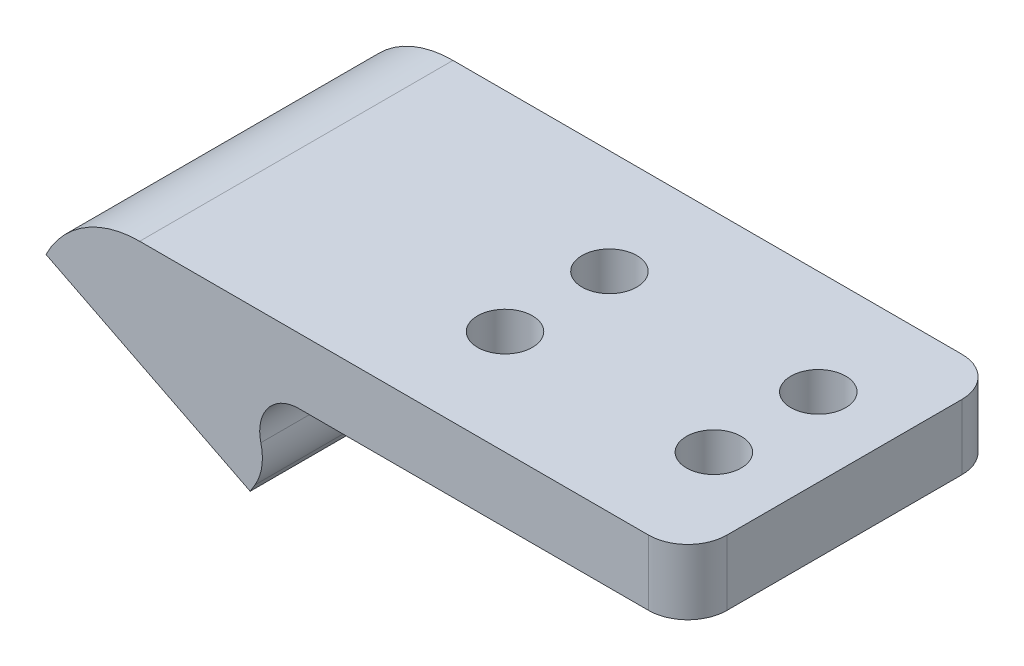
SolidWorks part; units mm, degrees
ref_plane "Plan de face" through (0, 0, 0) normal (0, 0, 1) x (1, 0, 0)
ref_plane "Plan de dessus" through (0, 0, 0) normal (0, 1, 0) x (1, 0, 0)
ref_plane "Plan de droite" through (0, 0, 0) normal (1, 0, 0) x (0, 0, -1)
sketch "Esquisse1" plane through (0, 0, 0) normal (0, 0, 1) x (1, 0, 0)
  line L1 (-6.5596, 0) -> (10.4404, 0)
  line L2 (-6.5596, 0) -> (-6.5596, 5)
  line L3 (-6.5596, 5) -> (10.4404, 5)
  line L4 (10.4404, 0) -> (10.4404, 5)
  dimension "D1" = 5
  dimension "D2" = 17
extrude "Boss.-Extru.1" add sketch "Esquisse1" along normal blind 24
sketch "Esquisse2" plane through (0, 0, 24) normal (0, 0, 1) x (1, 0, 0)
  line L0 (-6.5596, 5) -> (-16.4711, 5)
  line L1 (-16.4711, 5) -> (-0.5016, -3.0561)
  line L2 (-16.4711, 5) -> (-18.7231, 0.5359)
  line L3 (-18.7231, 0.5359) -> (-3.0805, -7.3553)
  line L4 (-3.0805, -7.3553) -> (-0.5016, -3.0561)
  line L5 (-6.5596, 5) -> (-6.5596, 0) construction
  line M4 (-6.5596, 5) -> (-6.5596, 0)
extrude "Boss.-Extru.2" add sketch "Esquisse2" against normal blind 24 contours L3 L4 L1 L2 | L0 L1 M4 region at (-9.8634, 3.3333, 24) region at (-9.6899, -1.2113, 24)
fillet "Congé1" radius 4 1 edges at (-0.5016, -3.0561, 12)
fillet "Congé2" radius 8 1 edges at (-16.4711, 5, 12)
fillet "Congé3" radius 3 1 edges at (-6.5596, 0, 12)
sketch "Esquisse3" plane through (10.4404, 0, 0) normal (1, 0, 0) x (0, 0, -1)
  line L1 (0, 0) -> (-24, 0)
  line L2 (0, 0) -> (0, 5)
  line L3 (0, 5) -> (-24, 5)
  line L4 (-24, 0) -> (-24, 5)
extrude "Boss.-Extru.3" add sketch "Esquisse3" along normal blind 20
sketch "Esquisse4" plane through (0, 5, 0) normal (0, 1, 0) x (1, 0, 0)
  line L0 (20.3965, -4) -> (12.3965, -4) construction
  line L1 (8.4404, -8) -> (24.4404, -8) construction
  line L2 (12.3965, -4) -> (12.3965, -20) construction
  line L3 (12.3965, -12) -> (30.4404, -12) construction
  line L4 (30.4404, 0) -> (30.4404, -24) construction
  line L5 (8.4404, -8) -> (8.4404, -16) construction
  line L6 (8.4404, -16) -> (24.4404, -16) construction
  line L7 (24.4404, -16) -> (24.4404, -8) construction
  circle A0 centre (12.3965, -4) radius 2.1 construction
  circle A1 centre (20.3965, -4) radius 2.1 construction
  circle A2 centre (12.3965, -20) radius 2.1 construction
  circle A3 centre (20.3965, -20) radius 2.1 construction
  circle A4 centre (12.3965, -20) radius 2.1
  circle A5 centre (8.4404, -8) radius 2.1
  circle A6 centre (24.4404, -8) radius 2.1
  circle A7 centre (8.4404, -16) radius 2.1
  circle A8 centre (24.4404, -16) radius 2.1
  point P21 (8.4404, -12)
  dimension "D4" = 4.2
  dimension "D3" = 4.2
  dimension "D1" = 8
  dimension "D2" = 16
  dimension "D5" = 8
  dimension "D6" = 16
  dimension "D7" = 6
extrude "Enlèv. mat.-Extru.1" cut sketch "Esquisse4" against normal blind 10 contours A2 | A3 | A1 | A0 | A7 | A6 | A8 | A5 region at (24.4404, 5, 8) region at (8.4404, 5, 16) region at (24.4404, 5, 16)
fillet "Congé4" radius 3 2 edges at (30.4404, 2.5, 0) (30.4404, 2.5, 24)
sketch "Esquisse5" plane through (-3.5827, -7.102, 0) normal (-0.4504, -0.8928, 0) x (0.8928, -0.4504, 0)
  line L0 (-16.9578, 12) -> (0.5625, 12) construction
  line L1 (-16.9578, 0) -> (-16.9578, 24) construction
  line L2 (0.5625, 0) -> (0.5625, 24) construction
  line L3 (-12.1477, 8.05) -> (-12.1477, 15.95) construction
  line L4 (-16.9578, 0) -> (0.5625, 0) construction
  line L5 (-8.1977, 0) -> (-8.1977, 24) construction
  line L6 (-16.9578, 24) -> (0.5625, 24) construction
  line L7 (-12.1477, 15.95) -> (-4.2477, 15.95) construction
  line L8 (-4.2477, 15.95) -> (-4.2477, 8.05) construction
  line L9 (-4.2477, 8.05) -> (-12.1477, 8.05) construction
  circle A0 centre (-12.1477, 15.95) radius 1.58 construction
  circle A1 centre (-4.2477, 15.95) radius 1.58 construction
  circle A2 centre (-12.1477, 8.05) radius 1.58 construction
  circle A3 centre (-4.2477, 8.05) radius 1.58 construction
  circle A4 centre (-12.1477, 8.05) radius 2.25
  circle A5 centre (-12.1477, 15.95) radius 2.25
  circle A6 centre (-4.2477, 15.95) radius 2.25
  circle A7 centre (-4.2477, 8.05) radius 2.25
  point P20 (-12.1477, 12)
  point P21 (-8.1977, 8.05)
  dimension "D2" = 3.16
  dimension "D3" = 4.5
  dimension "D1" = 7.9
extrude "Enlèv. mat.-Extru.2" cut sketch "Esquisse5" against normal blind 3
